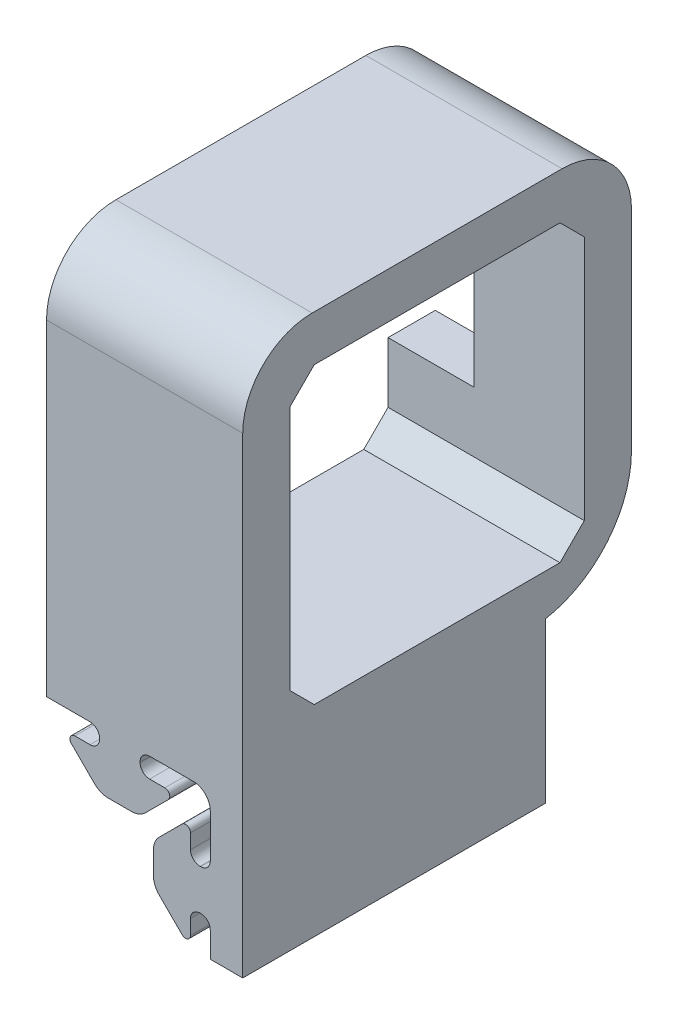
SolidWorks part; units mm, degrees
ref_plane "Front Plane" through (0, 0, 0) normal (0, 0, 1) x (1, 0, 0)
ref_plane "Top Plane" through (0, 0, 0) normal (0, 1, 0) x (1, 0, 0)
ref_plane "Right Plane" through (0, 0, 0) normal (1, 0, 0) x (0, 0, -1)
sketch "Sketch1" plane through (0, 0, 0) normal (0, 0, 1) x (1, 0, 0)
  line L0 (13.02, -7.9417) -> (17.7, -7.9417)
  line L1 (-10.5664, 13.02) -> (-10.5664, 70.02)
  line L2 (-10.5664, 70.02) -> (17.7, 70.02)
  line L3 (17.7, -7.9417) -> (17.7, 70.02)
  line L10 (12.7, -6.3331) -> (12.7, -7.9417) construction
  line L11 (13.02, -5.3171) -> (13.02, -4.2875)
  line L12 (11.651, -2.9185) -> (11.5392, -2.9185)
  line L13 (10.1702, -4.2875) -> (10.1702, -6.4021)
  line L14 (8.9631, -6.9029) -> (5.667, -3.6143)
  line L15 (4.8285, -1.5932) -> (4.8285, 1.5932)
  line L16 (5.667, 3.6143) -> (8.9631, 6.9029)
  line L17 (10.1702, 6.4021) -> (10.1702, 4.2875)
  line L18 (11.5392, 2.9185) -> (11.651, 2.9185)
  line L19 (13.02, 10.5773) -> (13.02, 4.2875)
  line L20 (6.3329, 13.02) -> (10.5626, 13.0198)
  line L22 (6.3329, 13.02) -> (4.2875, 13.02)
  line L23 (2.9185, 11.651) -> (2.9185, 11.5392)
  line L24 (4.2875, 10.1702) -> (6.4768, 10.1702)
  line L25 (6.981, 8.9509) -> (3.6723, 5.6497)
  line L26 (1.6558, 4.8158) -> (-1.6558, 4.8158)
  line L27 (-3.6723, 5.6497) -> (-6.981, 8.9509)
  line L28 (-6.4768, 10.1702) -> (-4.2875, 10.1702)
  line L29 (-2.9185, 11.5392) -> (-2.9185, 11.651)
  line L30 (-4.2875, 13.02) -> (-5.3171, 13.02)
  line L31 (-5.3171, 13.02) -> (-10.5664, 13.02)
  line L32 (13.02, -5.3171) -> (13.02, -7.9417)
  line L33 (13.02, -6.3331) -> (13.02, -7.9417) construction
  line L34 (13.02, 4.2875) -> (13.02, 5.3171) construction
  line L37 (5.3171, 13.02) -> (4.2875, 13.02) construction
  line L38 (-6.3331, 13.02) -> (-9.5504, 13.02) construction
  line L96 (12.7, -5.3171) -> (12.7, -4.2875) construction
  line L97 (11.651, -3.2385) -> (11.5392, -3.2385) construction
  line L98 (10.4902, -4.2875) -> (10.4902, -6.4021) construction
  line L99 (8.7371, -7.1294) -> (5.441, -3.8408) construction
  line L100 (4.5085, -1.5932) -> (4.5085, 1.5932) construction
  line L101 (5.441, 3.8408) -> (8.7371, 7.1294) construction
  line L102 (10.4902, 6.4021) -> (10.4902, 4.2875) construction
  line L103 (11.5392, 3.2385) -> (11.651, 3.2385) construction
  line L104 (12.7, 4.2875) -> (12.7, 5.3171) construction
  line L105 (12.7, 6.3331) -> (12.7, 9.5504) construction
  line L106 (9.5504, 12.7) -> (6.3331, 12.7) construction
  line L107 (5.3171, 12.7) -> (4.2875, 12.7) construction
  line L108 (3.2385, 11.651) -> (3.2385, 11.5392) construction
  line L109 (4.2875, 10.4902) -> (6.4768, 10.4902) construction
  line L110 (7.207, 8.7244) -> (3.8983, 5.4232) construction
  line L111 (1.6558, 4.4958) -> (-1.6558, 4.4958) construction
  line L112 (-3.8983, 5.4232) -> (-7.207, 8.7244) construction
  line L113 (-6.4768, 10.4902) -> (-4.2875, 10.4902) construction
  line L114 (-3.2385, 11.5392) -> (-3.2385, 11.651) construction
  line L115 (-4.2875, 12.7) -> (-5.3171, 12.7) construction
  line L116 (-6.3331, 12.7) -> (-9.5504, 12.7) construction
  arc A0 (13.02, -4.2875) -> (11.651, -2.9185) centre (11.651, -4.2875) ccw
  arc A1 (11.5392, -2.9185) -> (10.1702, -4.2875) centre (11.5392, -4.2875) ccw
  arc A2 (8.9631, -6.9029) -> (10.1702, -6.4021) centre (9.4628, -6.4021) ccw
  arc A3 (4.8285, -1.5932) -> (5.667, -3.6143) centre (7.6835, -1.5932) ccw
  arc A4 (5.667, 3.6143) -> (4.8285, 1.5932) centre (7.6835, 1.5932) ccw
  arc A5 (10.1702, 6.4021) -> (8.9631, 6.9029) centre (9.4628, 6.4021) ccw
  arc A6 (10.1702, 4.2875) -> (11.5392, 2.9185) centre (11.5392, 4.2875) ccw
  arc A7 (11.651, 2.9185) -> (13.02, 4.2875) centre (11.651, 4.2875) ccw
  arc A8 (4.2875, 13.02) -> (2.9185, 11.651) centre (4.2875, 11.651) ccw
  arc A9 (2.9185, 11.5392) -> (4.2875, 10.1702) centre (4.2875, 11.5392) ccw
  arc A10 (6.981, 8.9509) -> (6.4768, 10.1702) centre (6.4768, 9.4563) ccw
  arc A11 (1.6558, 4.8158) -> (3.6723, 5.6497) centre (1.6558, 7.6708) ccw
  arc A12 (-3.6723, 5.6497) -> (-1.6558, 4.8158) centre (-1.6558, 7.6708) ccw
  arc A13 (-6.4768, 10.1702) -> (-6.981, 8.9509) centre (-6.4768, 9.4563) ccw
  arc A14 (-4.2875, 10.1702) -> (-2.9185, 11.5392) centre (-4.2875, 11.5392) ccw
  arc A15 (-2.9185, 11.651) -> (-4.2875, 13.02) centre (-4.2875, 11.651) ccw
  arc A16 (13.02, 10.5773) -> (10.5626, 13.0198) centre (10.5918, 10.5918) ccw
  arc A17 (13.0198, 10.5625) -> (10.5626, 13.0198) centre (10.5918, 10.5918) ccw construction
  arc A114 (12.7, -5.3171) -> (12.7, -6.3331) centre (12.7, -5.8251) ccw construction
  arc A115 (12.7, -4.2875) -> (11.651, -3.2385) centre (11.651, -4.2875) ccw construction
  arc A116 (11.5392, -3.2385) -> (10.4902, -4.2875) centre (11.5392, -4.2875) ccw construction
  arc A117 (8.7371, -7.1294) -> (10.4902, -6.4021) centre (9.4628, -6.4021) ccw construction
  arc A118 (4.5085, -1.5932) -> (5.441, -3.8408) centre (7.6835, -1.5932) ccw construction
  arc A119 (5.441, 3.8408) -> (4.5085, 1.5932) centre (7.6835, 1.5932) ccw construction
  arc A120 (10.4902, 6.4021) -> (8.7371, 7.1294) centre (9.4628, 6.4021) ccw construction
  arc A121 (10.4902, 4.2875) -> (11.5392, 3.2385) centre (11.5392, 4.2875) ccw construction
  arc A122 (11.651, 3.2385) -> (12.7, 4.2875) centre (11.651, 4.2875) ccw construction
  arc A123 (12.7, 6.3331) -> (12.7, 5.3171) centre (12.7, 5.8251) ccw construction
  arc A124 (12.6998, 10.5664) -> (12.7, 9.5504) centre (12.7, 10.0584) ccw construction
  arc A125 (12.6998, 10.5664) -> (10.5664, 12.6998) centre (10.5918, 10.5918) ccw construction
  arc A126 (9.5504, 12.7) -> (10.5664, 12.6998) centre (10.0584, 12.7) ccw construction
  arc A127 (5.3171, 12.7) -> (6.3331, 12.7) centre (5.8251, 12.7) ccw construction
  arc A128 (4.2875, 12.7) -> (3.2385, 11.651) centre (4.2875, 11.651) ccw construction
  arc A129 (3.2385, 11.5392) -> (4.2875, 10.4902) centre (4.2875, 11.5392) ccw construction
  arc A130 (7.207, 8.7244) -> (6.4768, 10.4902) centre (6.4768, 9.4563) ccw construction
  arc A131 (1.6558, 4.4958) -> (3.8983, 5.4232) centre (1.6558, 7.6708) ccw construction
  arc A132 (-3.8983, 5.4232) -> (-1.6558, 4.4958) centre (-1.6558, 7.6708) ccw construction
  arc A133 (-6.4768, 10.4902) -> (-7.207, 8.7244) centre (-6.4768, 9.4563) ccw construction
  arc A134 (-4.2875, 10.4902) -> (-3.2385, 11.5392) centre (-4.2875, 11.5392) ccw construction
  arc A135 (-3.2385, 11.651) -> (-4.2875, 12.7) centre (-4.2875, 11.651) ccw construction
  arc A136 (-6.3331, 12.7) -> (-5.3171, 12.7) centre (-5.8251, 12.7) ccw construction
  arc A137 (-10.5664, 12.6998) -> (-9.5504, 12.7) centre (-10.0584, 12.7) ccw construction
  dimension "D1" = 57
  dimension "D6" = 5
  dimension "D8" = 0.32
  dimension "D7" = 6.2898
  dimension "D9" = 4.2297
extrude "Boss-Extrude1" add sketch "Sketch1" along normal blind 56 contours L3 L2 L1 L31 L30 A15 L29 A14 L28 A13 L27 A12 L26 A11 L25 A10 L24 A9 L23 A8 L22 L20 A16 L19 A7 L18 A6 L17 A5 L16 A4 L15 A3 L14 A2 L13 A1 L12 A0 L11 L32 L0
sketch "Sketch14" plane through (17.7, 0, 0) normal (1, 0, 0) x (0, 0, -1)
  line L4 (-56, -7.9417) -> (-56, 70.02) construction
  line L5 (0, -7.9417) -> (0, 70.02) construction
  line L6 (-56, 70.02) -> (0, 70.02) construction
  line L11 (0, 21.02) -> (-56, 21.02) construction
  line L12 (-28, 70.02) -> (-28, 21.02) construction
  line L14 (-49.2, 21.02) -> (-6.8, 21.02)
  line L15 (-49.2, 21.02) -> (-49.2, 63.42)
  line L16 (-49.2, 63.42) -> (-6.8, 63.42)
  line L17 (-6.8, 21.02) -> (-6.8, 63.42)
  point P14 (-28, 63.42)
  dimension "D1" = 42.4
  dimension "D2" = 42.4
other "AlignGroup1"
extrude "Cut-Extrude1" cut sketch "Sketch14" against normal blind 56
chamfer "Chamfer1" distance 3.5 4 edges at (3.5668, 21.02, 6.8) (3.5668, 21.02, 49.2) (3.5668, 63.42, 6.8) (3.5668, 63.42, 49.2)
fillet "Fillet1" radius 10 2 edges at (3.5668, 70.02, 56) (3.5668, 70.02, 0)
sketch "Sketch16" plane through (17.7, 0, 0) normal (1, 0, 0) x (0, 0, -1)
  line L1 (-56, -7.9417) -> (-43.6, -7.9417)
  line L2 (-56, -7.9417) -> (-56, 15.0583)
  line L3 (-56, 15.0583) -> (-43.6, 15.0583)
  line L4 (-43.6, -7.9417) -> (-43.6, 15.0583)
  dimension "D1" = 23
  dimension "D2" = 12.4
extrude "Cut-Extrude3" cut sketch "Sketch16" against normal through all
sketch "Sketch17" plane through (0, 0, 56) normal (0, 0, 1) x (1, 0, 0)
  line L0 (17.7, 42.22) -> (-10.5664, 42.22) construction
  line L2 (-13.62, 51.22) -> (1.8336, 51.22)
  line L3 (-13.62, 51.22) -> (-13.62, 33.22)
  line L4 (17.7, 24.52) -> (17.7, 59.92)
  line L5 (-10.5664, 24.52) -> (17.7, 24.52)
  line L6 (-10.5664, 59.92) -> (-10.5664, 24.52)
  line L7 (17.7, 59.92) -> (-10.5664, 59.92)
  line L8 (17.7, 24.52) -> (17.7, 59.92) construction
  line L9 (-10.5664, 24.52) -> (17.7, 24.52) construction
  line L10 (-10.5664, 59.92) -> (-10.5664, 24.52) construction
  line L11 (17.7, 59.92) -> (-10.5664, 59.92) construction
  line L12 (-13.62, 33.22) -> (1.8336, 33.22)
  line L13 (1.8336, 51.22) -> (1.8336, 33.22)
  point P10 (1.8336, 42.22)
  dimension "D2" = 18
  dimension "D3" = 12.4
  dimension "D1" = 0
extrude "Cut-Extrude4" cut sketch "Sketch17" against normal up to next
fillet "Fillet4" radius 15 1 edges at (3.5668, 15.0583, 56)
mirror "Mirror2" about plane through (-4.2875, 11.651, 0) normal (0, 0, 1) of bodies 126
sketch "Sketch18" plane through (0, 0, 0) normal (0, 0, -1) x (-1, 0, 0)
  line L0 (-23.6085, 16.9143) -> (-37.3681, 16.9143)
  line L1 (-23.6085, 72.8358) -> (16.3915, 72.8358)
  line L2 (-23.6085, 72.8358) -> (-23.6085, 16.9143)
  line L3 (-23.6085, -12.2016) -> (16.3915, -12.2016)
  line L4 (16.3915, 72.8358) -> (16.3915, -12.2016)
  line L5 (-37.3681, 16.9143) -> (-37.3681, -12.2016)
  line L6 (-37.3681, -12.2016) -> (-23.6085, -12.2016)
  dimension "D1" = 85.0374
  dimension "D2" = 40
extrude "Cut-Extrude5" cut sketch "Sketch18" against normal through all
